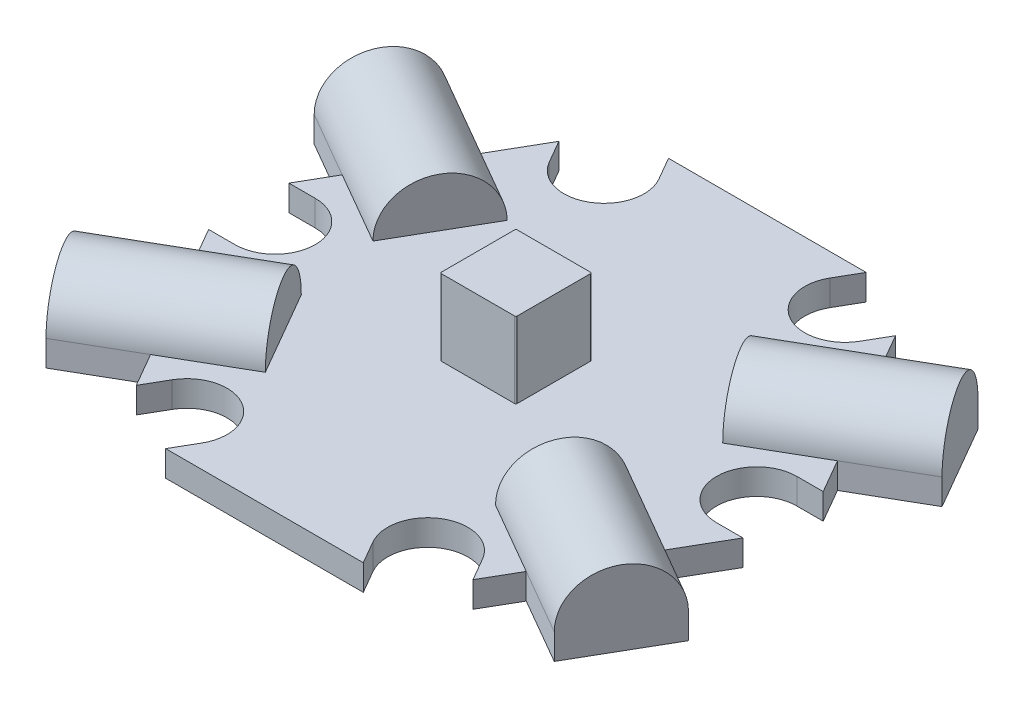
SolidWorks part; units mm, degrees
ref_plane "Front Plane" through (0, 0, 0) normal (0, 0, 1) x (1, 0, 0)
ref_plane "Top Plane" through (0, 0, 0) normal (0, 1, 0) x (1, 0, 0)
ref_plane "Right Plane" through (0, 0, 0) normal (1, 0, 0) x (0, 0, -1)
sketch "Sketch1" plane through (0, 0, 0) normal (0, 1, 0) x (1, 0, 0)
  line L7 (5.7412, 9.9441) -> (-5.7412, 9.9441)
  line L8 (-5.7412, 9.9441) -> (-11.4825, 0)
  line L9 (-11.4825, 0) -> (-5.7412, -9.9441)
  line L10 (-5.7412, -9.9441) -> (5.7412, -9.9441)
  line L11 (5.7412, -9.9441) -> (11.4825, 0)
  line L12 (11.4825, 0) -> (5.7412, 9.9441)
  circle A1 centre (0, 0) radius 9.9441 construction
extrude "Boss-Extrude1" add sketch "Sketch1" along normal blind 1.016
sketch "Sketch2" plane through (0, 1.016, 0) normal (0, 1, 0) x (1, 0, 0)
  line L6 (9.525, 1.5875) -> (13.1378, 1.5875)
  line L12 (9.525, -1.5875) -> (13.1378, -1.5875)
  line L13 (13.1378, 1.5875) -> (13.1378, -1.5875)
  arc A1 (9.525, 1.5875) -> (9.525, -1.5875) centre (9.525, 0) ccw
  dimension "D1" = 9.525
extrude "Cut-Extrude1" cut sketch "Sketch2" against normal blind 1.016
ref_axis "Axis1" through (0, 4.2168, 0) along (0, -1, 0)
pattern_circular "CirPattern1" count 6 every 60 about axis through (0, 4.2168, 0) along (0, -1, 0) of "Cut-Extrude1"
sketch "Sketch3" plane through (0, 1.016, 0) normal (0, 1, 0) x (1, 0, 0)
  line L1 (-1.5, -1.5) -> (-1.5, 1.5)
  line L2 (-1.5, -1.5) -> (1.5, -1.5)
  line L3 (-1.5, 1.5) -> (1.5, 1.5)
  line L4 (1.5, -1.5) -> (1.5, 1.5)
  line L6 (-1.5, 1.5) -> (-0.0012, 0.0012) construction
  point P9 (0, 0)
  dimension "D1" = 3
  dimension "D2" = 3
extrude "Boss-Extrude2" add sketch "Sketch3" along normal blind 3
fillet "Fillet1" radius 0.0508 1 edges at (1.5, 2.516, 1.5)
fillet "Fillet2" radius 0.0508 1 edges at (-1.5, 2.516, -1.5)
fillet "Fillet3" radius 0.0508 1 edges at (1.5, 2.516, -1.5)
fillet "Fillet4" radius 0.0508 1 edges at (-1.5, 2.516, 1.5)
sketch "Sketch4" plane through (0, 1.016, 0) normal (0, 1, 0) x (1, 0, 0)
  line L0 (-8.4528, -3.1242) -> (-6.5097, -6.4897)
  line L1 (-8.4528, -3.1242) -> (-6.4951, -1.9939)
  line L2 (-6.5097, -6.4897) -> (-4.552, -5.3594)
  line L3 (-6.4951, -1.9939) -> (-4.552, -5.3594)
  line L4 (-8.4528, -3.1242) -> (-4.552, -5.3594) construction
  line L5 (-6.5097, -6.4897) -> (-6.4951, -1.9939) construction
  line L11 (-1.5, 1.4492) -> (-1.5, -1.4492) construction
  point P1 (-6.5024, -4.2418)
  point P13 (-1.5, 0)
  dimension "D1" = 3.8862
  dimension "D2" = 2.2606
  dimension "D3" = 6.5024
  dimension "D4" = 4.2418
ref_plane "Plane1" through (-5.7347, 0, 3.3109) normal (-0.866, 0, 0.5) x (0.5, 0, 0.866)
sketch "Sketch5" plane through (-5.7347, 0, 3.3109) normal (-0.866, 0, 0.5) x (0.5, 0, 0.866)
  line L0 (-1.5208, 1.016) -> (2.3654, 1.016) construction
  line L1 (-1.5208, 1.016) -> (2.3654, 1.016)
  arc A0 (-1.5208, 1.016) -> (2.3654, 1.016) centre (0.4223, 1.016) cw
extrude "Boss-Extrude3" add sketch "Sketch5" along normal blind 6.35 contours A0 L1 region at (-5.5235, 1.8407, 3.6766)
pattern_circular "CirPattern2" count 2 every 60 about axis through (0, 4.2168, 0) along (0, -1, 0) of "Boss-Extrude3"
sketch "Sketch7" plane through (0, 1.016, 0) normal (0, -1, 0) x (1, 0, 0)
  line L4 (-11.9943, 5.1689) -> (-9.3722, 3.655)
  line L5 (-9.3722, 3.655) -> (-7.4291, 7.0206)
  line L6 (-7.4291, 7.0206) -> (-10.0512, 8.5344)
  line L7 (-10.0512, 8.5344) -> (-11.9943, 5.1689)
  line L8 (-11.9943, 5.1689) -> (-9.3722, 3.655)
  line L9 (-9.3722, 3.655) -> (-7.4291, 7.0206)
  line L10 (-7.4291, 7.0206) -> (-10.0512, 8.5344)
  line L11 (-10.0512, 8.5344) -> (-11.9943, 5.1689)
  dimension "D1" = 0
extrude "Boss-Extrude4" add sketch "Sketch7" along normal up to surface (1.016 mm away) up to face at (0, 0, 0)
sketch "Sketch8" plane through (0, 1.016, 0) normal (0, -1, 0) x (1, 0, 0)
  line L4 (-10.4735, -7.803) -> (-7.8514, -6.2891)
  line L5 (-7.8514, -6.2891) -> (-9.7945, -2.9235)
  line L6 (-9.7945, -2.9235) -> (-12.4166, -4.4374)
  line L7 (-12.4166, -4.4374) -> (-10.4735, -7.803)
  line L8 (-10.4735, -7.803) -> (-7.8514, -6.2891)
  line L9 (-7.8514, -6.2891) -> (-9.7945, -2.9235)
  line L10 (-9.7945, -2.9235) -> (-12.4166, -4.4374)
  line L11 (-12.4166, -4.4374) -> (-10.4735, -7.803)
  dimension "D1" = 0
extrude "Boss-Extrude5" add sketch "Sketch8" along normal up to surface (1.016 mm away) up to face at (-1.3874, 0, 0.8707)
ref_plane "Plane2" through (0, 0, 0) normal (1, 0, 0) x (0, -1, 0)
mirror "Mirror1" about plane through (0, 0, 0) normal (1, 0, 0) of "CirPattern2", "Boss-Extrude5", "Boss-Extrude4", "Boss-Extrude3"
